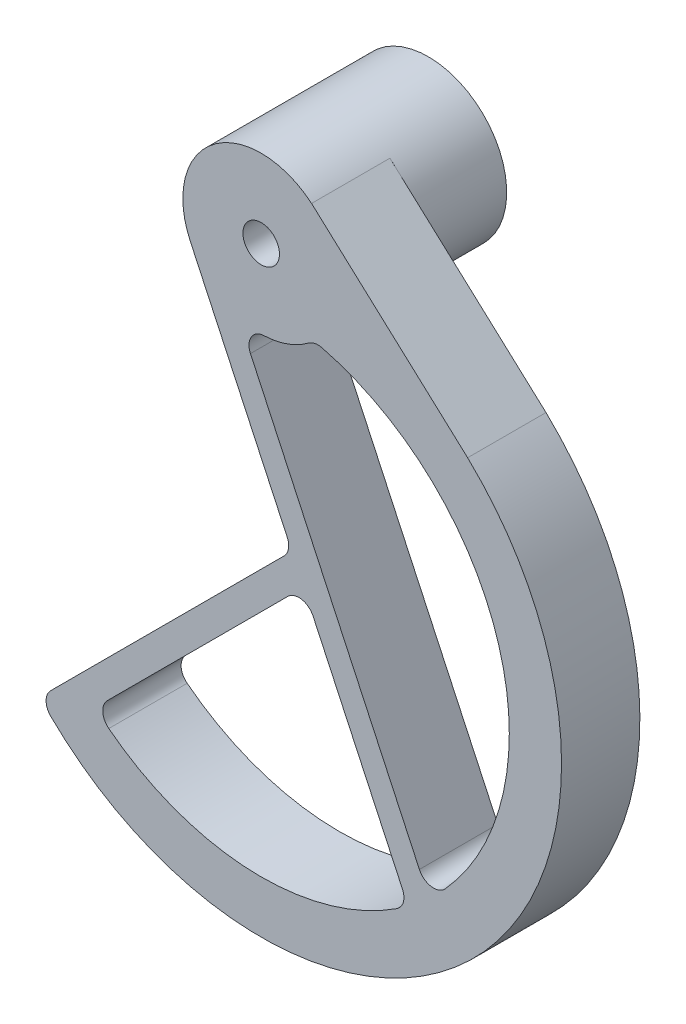
SolidWorks part; units mm, degrees
material "ABS"
ref_plane "正面" through (0, 0, 0) normal (0, 0, 1) x (1, 0, 0)
ref_plane "平面" through (0, 0, 0) normal (0, 1, 0) x (1, 0, 0)
ref_plane "右側面" through (0, 0, 0) normal (1, 0, 0) x (0, 0, -1)
sketch "ｽｹｯﾁ1" plane through (0, 0, 0) normal (0, 0, 1) x (1, 0, 0)
  line L1 (9.9336, 0.7043) -> (27.0462, -35.9938)
  line L2 (9.6418, 68.9907) -> (39.5241, 41.7624)
  line L4 (4.3888, 7.9244) -> (-40.3035, -36.7679)
  line L5 (5.0933, 1.5578) -> (-29.4572, -32.9928)
  line L6 (-13.5946, 51.1607) -> (4.9864, 11.3135)
  line L7 (30.2877, -31.1143) -> (-2.0547, 38.2444)
  arc A0 (-40.2839, -41.0299) -> (37.9168, 43.2269) centre (0, 0) ccw
  arc A1 (-29.1788, -37.4813) -> (25.9673, -39.7737) centre (0, 0) ccw
  arc A2 (0.5535, 42.5102) -> (9.0577, 45.5435) centre (0, 57.5) ccw
  arc A3 (35.2318, -31.8586) -> (11.602, 46.0613) centre (0, 0) ccw
  arc A4 (10.5469, 68.1659) -> (-13.5946, 51.1607) centre (0, 57.5) ccw
  arc A5 (-40.3035, -36.7679) -> (-40.2839, -41.0299) centre (-38.1821, -38.8893) ccw
  arc A6 (-29.4572, -32.9928) -> (-29.1788, -37.4813) centre (-27.3359, -35.1141) ccw
  arc A7 (27.0462, -35.9938) -> (25.9673, -39.7737) centre (24.3273, -37.2617) cw
  arc A8 (5.0933, 1.5578) -> (9.9336, 0.7043) centre (7.2147, -0.5635) cw
  arc A9 (35.2318, -31.8586) -> (30.2877, -31.1143) centre (33.0067, -29.8464) cw
  arc A10 (4.9864, 11.3135) -> (4.3888, 7.9244) centre (2.2675, 10.0457) cw
  arc A11 (-2.0547, 38.2444) -> (0.5535, 42.5102) centre (0.6642, 39.5123) cw
  arc A12 (11.602, 46.0613) -> (9.0577, 45.5435) centre (10.8692, 43.1522) ccw
  point P24 (8.1229, 4.5874)
  dimension "D1" = 3
  dimension "D2" = 3
  dimension "D3" = 3
  dimension "D4" = 3
  dimension "D5" = 3
  dimension "D6" = 3
  dimension "D7" = 3
  dimension "D8" = 3
extrude "ﾎﾞｽ - 押し出し1" add sketch "ｽｹｯﾁ1" along normal blind 15 contours L6 A10 L4 A5 A0 L2 A4 A12 A3 A9 L7 A11 A2 L5 A8 L1 A7 A1 A6 region at (8.9951, 67.3719, 0)
sketch "ｽｹｯﾁ6" plane through (0, 0, 15) normal (0, 0, 1) x (1, 0, 0)
  circle A0 centre (0, 57.5) radius 3.5
  dimension "D1" = 7
extrude "ｶｯﾄ - 押し出し2" cut sketch "ｽｹｯﾁ6" against normal blind 15
sketch "ｽｹｯﾁ11" plane through (0, 0, 0) normal (0, 0, -1) x (-1, 0, 0)
  circle A0 centre (0, 57.5) radius 15
  circle A1 centre (0, 57.5) radius 3.5
extrude "ﾎﾞｽ - 押し出し3" add sketch "ｽｹｯﾁ11" along normal blind 17
sketch "ｽｹｯﾁ12" plane through (0, 0, -17) normal (0, 0, -1) x (-1, 0, 0)
  circle A0 centre (0, 57.5) radius 10.1
extrude "ｶｯﾄ - 押し出し6" cut sketch "ｽｹｯﾁ12" against normal blind 2
